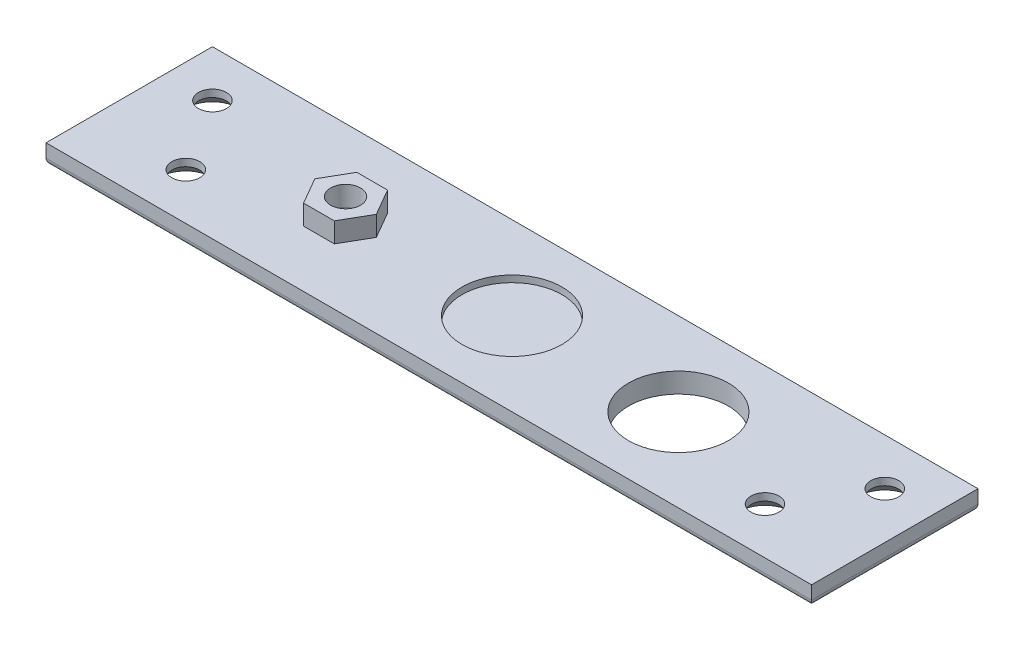
SolidWorks part; units mm, degrees
material "Aço cromo inoxidável"
ref_plane "Plano frontal" through (0, 0, 0) normal (0, 0, 1) x (1, 0, 0)
ref_plane "Plano superior" through (0, 0, 0) normal (0, 1, 0) x (1, 0, 0)
ref_plane "Plano direito" through (0, 0, 0) normal (1, 0, 0) x (0, 0, -1)
sketch "Esboço1" plane through (0, 0, 0) normal (0, 1, 0) x (1, 0, 0)
  line L1 (-57.5, -12.5) -> (57.5, -12.5)
  line L2 (-57.5, -12.5) -> (-57.5, 12.5)
  line L3 (-57.5, 12.5) -> (57.5, 12.5)
  line L4 (57.5, -12.5) -> (57.5, 12.5)
  line L5 (0, 12.5) -> (0, -12.5) construction
  line L6 (-57.5, 0) -> (57.5, 0) construction
  point P0 (0, 0)
  dimension "D1" = 115
  dimension "D2" = 25
extrude "Ressalto-extrusão1" add sketch "Esboço1" along normal mid plane 3
sketch "Esboço2" plane through (0, 1.5, 0) normal (0, 1, 0) x (1, 0, 0)
  circle A0 centre (0, 0) radius 7.5
  circle A1 centre (25, 0) radius 7.5
  circle A2 centre (-25, 0) radius 2.5 construction
  dimension "D1" = 15
  dimension "D2" = 25
  dimension "D4" = 5
  dimension "D3" = 25
extrude "Corte-extrusão1" cut sketch "Esboço2" against normal through all contours A1
extrude "Corte-extrusão2" cut sketch "Esboço2<3>" against normal blind 1 contours A0
sketch "Esboço2<3>" plane through (0, 1.5, 0) normal (0, 1, 0) x (1, 0, 0) same geometry as "Esboço2"
hole_wizard "Escareado para SFHCS M51" positions "Esboço3" profile "Esboço4" countersink size "M5" standard "Ansi Metric" end condition through all
sketch "Esboço3" plane through (0, -1.5, 0) normal (0, -1, 0) x (-1, 0, 0)
  line L0 (-57.5, -12.5) -> (-57.5, 12.5) construction
  line L1 (57.5, -12.5) -> (-57.5, -12.5) construction
  line L2 (-57.5, 12.5) -> (57.5, 12.5) construction
  line L3 (0, 1.65) -> (0, -1.65) construction
  point P0 (-50.5, 5.5)
  point P2 (-43.5, -5.5)
  point P18 (43.5, -5.5)
  point P19 (50.5, 5.5)
  dimension "D1" = 7
  dimension "D2" = 7
  dimension "D3" = 7
  dimension "D4" = 14
sketch "Esboço4" plane through (50.5, -1.5, -5.5) normal (1, 0, 0) x (0, 0, -1)
  line L0 (0, 0) -> (0, 3)
  line L1 (0, 3) -> (2.1, 3)
  line L2 (2.1, 3) -> (2.1, 1.9)
  line L3 (2.1, 1.9) -> (4, 0)
  line L5 (4, 0) -> (0, 0)
  line L6 (-2.1, 1.9) -> (-4, 0) construction
  line L11 (0, -6.35) -> (0, 107.95) construction
  dimension "Thru Hole Dia." = 4.2
  dimension "Thru Hole Depth" = 3
  dimension "Near C'Sink Dia." = 8
  dimension "Near C'Sink Angle" = 90
fillet "Filete1" radius 1 4 edges at (0, -1.5, -12.5) (-57.5, -1.5, 0) (57.5, -1.5, 0) (0, -1.5, 12.5)
hole_wizard "Escareado para SFHCS M41" positions "Esboço5" profile "Esboço6" countersink size "M4" standard "Ansi Metric" end condition through all
sketch "Esboço5" plane through (0, -1.5, 0) normal (0, -1, 0) x (-1, 0, 0)
  point P0 (25, 0)
sketch "Esboço6" plane through (-25, -1.5, 0) normal (1, 0, 0) x (0, 0, -1)
  line L0 (0, 0) -> (0, 3)
  line L1 (0, 3) -> (2.25, 3)
  line L2 (2.25, 3) -> (2.25, 2.23)
  line L3 (2.25, 2.23) -> (4.48, 0)
  line L5 (4.48, 0) -> (0, 0)
  line L6 (-2.25, 2.23) -> (-4.48, 0) construction
  line L11 (0, -6.35) -> (0, 107.95) construction
  dimension "Thru Hole Dia." = 4.5
  dimension "Thru Hole Depth" = 3
  dimension "Near C'Sink Dia." = 8.96
  dimension "Near C'Sink Angle" = 90
sketch "Esboço7" plane through (0, 1.5, 0) normal (0, 1, 0) x (1, 0, 0)
  line L1 (-22.6906, -4) -> (-20.3812, 0)
  line L2 (-20.3812, 0) -> (-22.6906, 4)
  line L3 (-22.6906, 4) -> (-27.3094, 4)
  line L4 (-27.3094, 4) -> (-29.6188, 0)
  line L5 (-29.6188, 0) -> (-27.3094, -4)
  line L6 (-27.3094, -4) -> (-22.6906, -4)
  circle A0 centre (-25, 0) radius 4 construction
  circle A1 centre (-25, 0) radius 2.25 construction
  circle A2 centre (-25, 0) radius 2.25
  point P12 (-20.3812, 0)
  dimension "D1" = 8
extrude "Ressalto-extrusão2" add sketch "Esboço7" along normal blind 3 separate body
